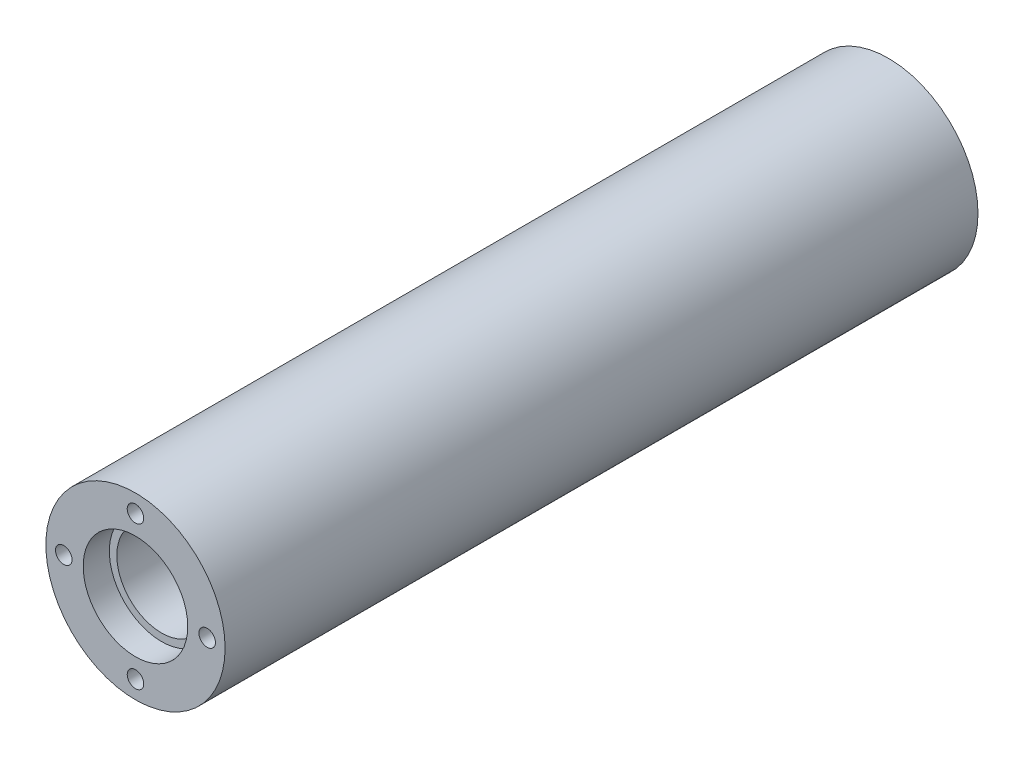
SolidWorks part; units mm, degrees
other "Markup1"
sketch "Sketch4" plane through (19.05, 19.05, 152.4) normal (0.8805, 0.4318, 0.1958) x (0.1841, 0.0692, -0.9805)
ref_plane "Front Plane" through (0, 0, 0) normal (0, 0, 1) x (1, 0, 0)
ref_plane "Top Plane" through (0, 0, 0) normal (0, 1, 0) x (1, 0, 0)
ref_plane "Right Plane" through (0, 0, 0) normal (1, 0, 0) x (0, 0, -1)
sketch "Sketch1" plane through (0, 0, 0) normal (0, 0, 1) x (1, 0, 0)
  circle A0 centre (0, 0) radius 19.05
  circle A1 centre (0, 0) radius 9.525
  dimension "D1" = 38.1
  dimension "D2" = 19.05
extrude "Boss-Extrude1" add sketch "Sketch1" along normal blind 160.02
sketch "Sketch2" plane through (0, 0, 0) normal (0, 0, -1) x (-1, 0, 0)
  circle A0 centre (0, 15.24) radius 1.7526
  circle A1 centre (15.24, 0) radius 1.7526
  circle A2 centre (0, -15.24) radius 1.7526
  circle A3 centre (-15.24, 0) radius 1.7526
  point P12 (0, 0)
  dimension "D1" = 3.5052
  dimension "D2" = 15.24
  dimension "D3" = 4
extrude "Cut-Extrude1" cut sketch "Sketch2" against normal blind 9.525
sketch "Sketch3" plane through (0, 0, 160.02) normal (0, 0, 1) x (1, 0, 0)
  circle A0 centre (0, 15.24) radius 1.7526
  circle A1 centre (15.24, 0) radius 1.7526
  circle A2 centre (0, -15.24) radius 1.7526
  circle A3 centre (-15.24, 0) radius 1.7526
  point P2 (0, 0)
  point P9 (0, 0)
  point P12 (0, 0)
  point P15 (0, 0)
  point P16 (0, 0)
  dimension "D2" = 3.5052
  dimension "D1" = 15.24
  dimension "D3" = 4
extrude "Cut-Extrude2" cut sketch "Sketch3" against normal blind 9.525
sketch "Sketch6" plane through (0, 0, 160.02) normal (0, 0, 1) x (1, 0, 0)
  circle A0 centre (0, 0) radius 11.1125
  dimension "D1" = 22.225
extrude "Cut-Extrude3" cut sketch "Sketch6" against normal blind 5.5562
sketch "Sketch7" plane through (0, 0, 0) normal (0, 0, -1) x (-1, 0, 0)
  circle A0 centre (0, 0) radius 11.1125
  dimension "D1" = 22.225
extrude "Cut-Extrude4" cut sketch "Sketch7" against normal blind 5.5562
